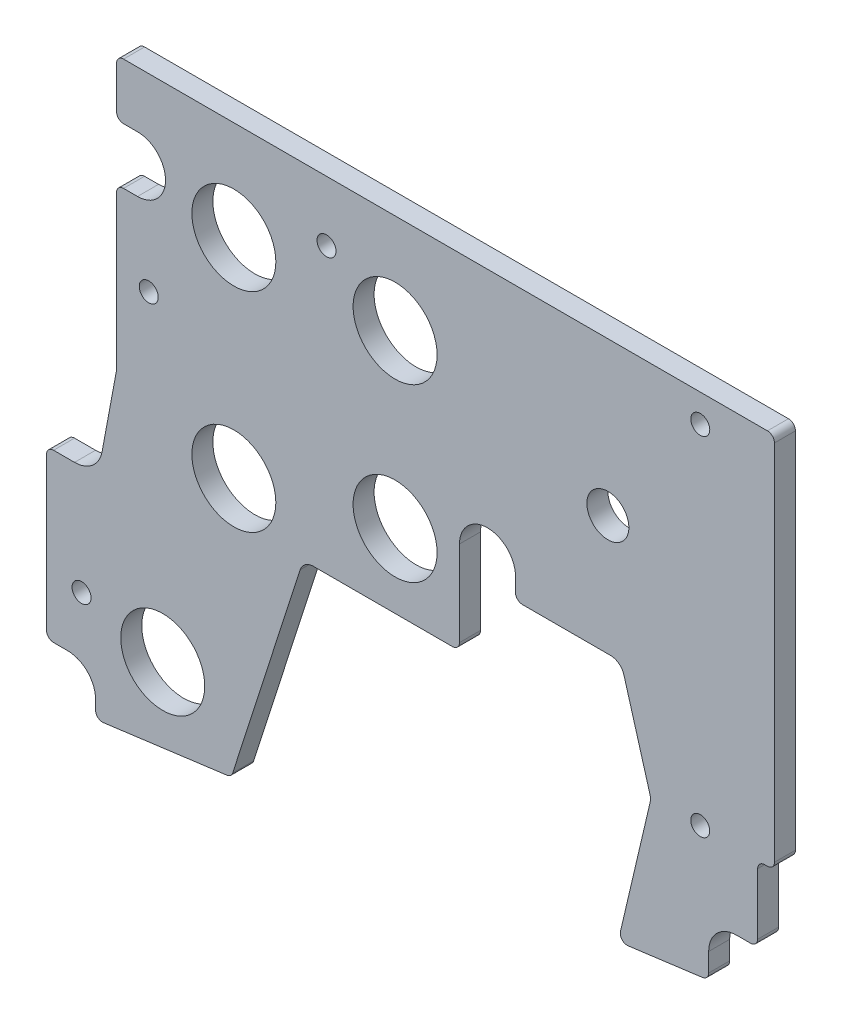
SolidWorks part; units mm, degrees
ref_plane "Front Plane" through (0, 0, 0) normal (0, 0, 1) x (1, 0, 0)
ref_plane "Top Plane" through (0, 0, 0) normal (0, 1, 0) x (1, 0, 0)
ref_plane "Right Plane" through (0, 0, 0) normal (1, 0, 0) x (0, 0, -1)
sketch "Sketch1" plane through (0, 0, 0) normal (0, 0, 1) x (1, 0, 0)
  line L24 (-1.5875, -85.5345) -> (-1.5875, -3.175)
  line L25 (-3.175, -1.5875) -> (-149.225, -1.5875)
  line L26 (-150.8125, -3.175) -> (-150.8125, -12.7)
  line L27 (-149.225, -14.2875) -> (-146.05, -14.2875)
  line L28 (-146.05, -26.9875) -> (-149.225, -26.9875)
  line L29 (-150.8125, -28.575) -> (-150.8125, -63.3539)
  line L30 (-150.8392, -63.6437) -> (-154.0942, -81.1696)
  line L31 (-160.3375, -86.36) -> (-165.1, -86.36)
  line L32 (-166.6875, -87.9475) -> (-166.6875, -122.5455)
  line L33 (-165.1, -124.133) -> (-161.925, -124.133)
  line L34 (-155.575, -130.483) -> (-155.575, -132.6404)
  line L35 (-153.7803, -134.2144) -> (-125.7711, -130.5269)
  line L36 (-124.467, -129.4389) -> (-109.1805, -81.8956)
  line L37 (-106.1579, -79.6925) -> (-74.6125, -79.6925)
  line L38 (-73.025, -78.105) -> (-73.025, -58.7375)
  line L39 (-60.325, -58.7375) -> (-60.325, -61.9125)
  line L40 (-58.7375, -63.5) -> (-38.7866, -63.5)
  line L41 (-35.7358, -65.7958) -> (-29.8313, -86.2841)
  line L42 (-29.7909, -87.8878) -> (-36.5223, -116.6102)
  line L43 (-34.7695, -118.5463) -> (-17.8903, -116.3241)
  line L44 (-16.51, -114.7502) -> (-16.51, -110.5169)
  line L45 (-10.16, -104.1528) -> (-6.985, -104.1528)
  line L46 (-5.3975, -102.5653) -> (-5.3975, -88.7095)
  line L47 (-3.81, -87.122) -> (-3.175, -87.122)
  line L48 (-1.5875, -85.5345) -> (-1.5875, -3.175)
  line L49 (-3.175, -1.5875) -> (-149.225, -1.5875)
  line L50 (-150.8125, -3.175) -> (-150.8125, -12.7)
  line L51 (-149.225, -14.2875) -> (-146.05, -14.2875)
  line L52 (-146.05, -26.9875) -> (-149.225, -26.9875)
  line L53 (-150.8125, -28.575) -> (-150.8125, -63.3539)
  line L54 (-150.8392, -63.6437) -> (-154.0942, -81.1696)
  line L55 (-160.3375, -86.36) -> (-165.1, -86.36)
  line L56 (-166.6875, -87.9475) -> (-166.6875, -122.5455)
  line L57 (-165.1, -124.133) -> (-161.925, -124.133)
  line L58 (-155.575, -130.483) -> (-155.575, -132.6404)
  line L59 (-153.7803, -134.2144) -> (-125.7711, -130.5269)
  line L60 (-124.467, -129.4389) -> (-109.1805, -81.8956)
  line L61 (-106.1579, -79.6925) -> (-74.6125, -79.6925)
  line L62 (-73.025, -78.105) -> (-73.025, -58.7375)
  line L63 (-60.325, -58.7375) -> (-60.325, -61.9125)
  line L64 (-58.7375, -63.5) -> (-38.7866, -63.5)
  line L65 (-35.7358, -65.7958) -> (-29.8313, -86.2841)
  line L66 (-29.7909, -87.8878) -> (-36.5223, -116.6102)
  line L67 (-34.7695, -118.5463) -> (-17.8903, -116.3241)
  line L68 (-16.51, -114.7502) -> (-16.51, -110.5169)
  line L69 (-10.16, -104.1528) -> (-6.985, -104.1528)
  line L70 (-5.3975, -102.5653) -> (-5.3975, -88.7095)
  line L71 (-3.81, -87.122) -> (-3.175, -87.122)
  arc A24 (-3.175, -87.122) -> (-1.5875, -85.5345) centre (-3.175, -85.5345) ccw
  arc A25 (-1.5875, -3.175) -> (-3.175, -1.5875) centre (-3.175, -3.175) ccw
  arc A26 (-149.225, -1.5875) -> (-150.8125, -3.175) centre (-149.225, -3.175) ccw
  arc A27 (-150.8125, -12.7) -> (-149.225, -14.2875) centre (-149.225, -12.7) ccw
  arc A28 (-146.05, -26.9875) -> (-146.05, -14.2875) centre (-146.05, -20.6375) ccw
  arc A29 (-149.225, -26.9875) -> (-150.8125, -28.575) centre (-149.225, -28.575) ccw
  arc A30 (-150.8392, -63.6437) -> (-150.8125, -63.3539) centre (-152.4, -63.3539) ccw
  arc A31 (-160.3375, -86.36) -> (-154.0942, -81.1696) centre (-160.3375, -80.01) ccw
  arc A32 (-165.1, -86.36) -> (-166.6875, -87.9475) centre (-165.1, -87.9475) ccw
  arc A33 (-166.6875, -122.5455) -> (-165.1, -124.133) centre (-165.1, -122.5455) ccw
  arc A34 (-155.575, -130.483) -> (-161.925, -124.133) centre (-161.925, -130.483) ccw
  arc A35 (-155.575, -132.6404) -> (-153.7803, -134.2144) centre (-153.9875, -132.6404) ccw
  arc A36 (-125.7711, -130.5269) -> (-124.467, -129.4389) centre (-125.9783, -128.953) ccw
  arc A37 (-106.1579, -79.6925) -> (-109.1805, -81.8956) centre (-106.1579, -82.8675) ccw
  arc A38 (-74.6125, -79.6925) -> (-73.025, -78.105) centre (-74.6125, -78.105) ccw
  arc A39 (-60.325, -58.7375) -> (-73.025, -58.7375) centre (-66.675, -58.7375) ccw
  arc A40 (-60.325, -61.9125) -> (-58.7375, -63.5) centre (-58.7375, -61.9125) ccw
  arc A41 (-35.7358, -65.7958) -> (-38.7866, -63.5) centre (-38.7866, -66.675) ccw
  arc A42 (-29.7909, -87.8878) -> (-29.8313, -86.2841) centre (-32.8822, -87.1633) ccw
  arc A43 (-36.5223, -116.6102) -> (-34.7695, -118.5463) centre (-34.9767, -116.9724) ccw
  arc A44 (-17.8903, -116.3241) -> (-16.51, -114.7502) centre (-18.0975, -114.7502) ccw
  arc A45 (-10.16, -104.1528) -> (-16.51, -110.5169) centre (-10.16, -110.5028) ccw
  arc A46 (-6.985, -104.1528) -> (-5.3975, -102.5653) centre (-6.985, -102.5653) ccw
  arc A47 (-3.81, -87.122) -> (-5.3975, -88.7095) centre (-3.81, -88.7095) ccw
  arc A48 (-3.175, -87.122) -> (-1.5875, -85.5345) centre (-3.175, -85.5345) ccw
  arc A49 (-1.5875, -3.175) -> (-3.175, -1.5875) centre (-3.175, -3.175) ccw
  arc A50 (-149.225, -1.5875) -> (-150.8125, -3.175) centre (-149.225, -3.175) ccw
  arc A51 (-150.8125, -12.7) -> (-149.225, -14.2875) centre (-149.225, -12.7) ccw
  arc A52 (-146.05, -26.9875) -> (-146.05, -14.2875) centre (-146.05, -20.6375) ccw
  arc A53 (-149.225, -26.9875) -> (-150.8125, -28.575) centre (-149.225, -28.575) ccw
  arc A54 (-150.8392, -63.6437) -> (-150.8125, -63.3539) centre (-152.4, -63.3539) ccw
  arc A55 (-160.3375, -86.36) -> (-154.0942, -81.1696) centre (-160.3375, -80.01) ccw
  arc A56 (-165.1, -86.36) -> (-166.6875, -87.9475) centre (-165.1, -87.9475) ccw
  arc A57 (-166.6875, -122.5455) -> (-165.1, -124.133) centre (-165.1, -122.5455) ccw
  arc A58 (-155.575, -130.483) -> (-161.925, -124.133) centre (-161.925, -130.483) ccw
  arc A59 (-155.575, -132.6404) -> (-153.7803, -134.2144) centre (-153.9875, -132.6404) ccw
  arc A60 (-125.7711, -130.5269) -> (-124.467, -129.4389) centre (-125.9783, -128.953) ccw
  arc A61 (-106.1579, -79.6925) -> (-109.1805, -81.8956) centre (-106.1579, -82.8675) ccw
  arc A62 (-74.6125, -79.6925) -> (-73.025, -78.105) centre (-74.6125, -78.105) ccw
  arc A63 (-60.325, -58.7375) -> (-73.025, -58.7375) centre (-66.675, -58.7375) ccw
  arc A64 (-60.325, -61.9125) -> (-58.7375, -63.5) centre (-58.7375, -61.9125) ccw
  arc A65 (-35.7358, -65.7958) -> (-38.7866, -63.5) centre (-38.7866, -66.675) ccw
  arc A66 (-29.7909, -87.8878) -> (-29.8313, -86.2841) centre (-32.8822, -87.1633) ccw
  arc A67 (-36.5223, -116.6102) -> (-34.7695, -118.5463) centre (-34.9767, -116.9724) ccw
  arc A68 (-17.8903, -116.3241) -> (-16.51, -114.7502) centre (-18.0975, -114.7502) ccw
  arc A69 (-10.16, -104.1528) -> (-16.51, -110.5169) centre (-10.16, -110.5028) ccw
  arc A70 (-6.985, -104.1528) -> (-5.3975, -102.5653) centre (-6.985, -102.5653) ccw
  arc A71 (-3.81, -87.122) -> (-5.3975, -88.7095) centre (-3.81, -88.7095) ccw
  dimension "D1" = 0
extrude "Boss-Extrude1" add sketch "Sketch1" along normal blind 4.7625
hole_wizard "#6 Clearance Hole1" positions "Sketch3" profile "Sketch2" hole size "#6" standard "ANSI Inch" end condition through all
sketch "Sketch3" plane through (0, 0, 4.7625) normal (0, 0, 1) x (1, 0, 0)
  point P0 (-103.1875, -15.24)
  point P3 (-18.415, -7.9375)
  point P6 (-143.51, -44.45)
  point P9 (-158.75, -111.125)
  point P12 (-18.415, -86.741)
sketch "Sketch2" plane through (-103.1875, -15.24, 4.7625) normal (1, 0, 0) x (0, -1, 0)
  line L0 (0, 0) -> (0, 4.7625)
  line L1 (0, 4.7625) -> (2.1526, 4.7625)
  line L2 (2.1526, 4.7625) -> (2.1526, 0)
  line L5 (2.1526, 0) -> (0, 0)
  line L11 (0, -6.35) -> (0, 107.95) construction
  dimension "Thru Hole Dia." = 4.3053
  dimension "Thru Hole Depth" = 4.7625
sketch "Sketch5" plane through (0, 0, 4.7625) normal (0, 0, 1) x (1, 0, 0)
  circle A0 centre (-124.206, -24.13) radius 9.525
  circle A1 centre (-87.63, -24.13) radius 9.525
  circle A2 centre (-87.63, -62.992) radius 9.525
  circle A3 centre (-124.206, -71.4375) radius 9.525
  circle A4 centre (-140.335, -115.57) radius 9.525
  circle A5 centre (-39.37, -36.322) radius 4.7625
  dimension "D1" = 19.05
  dimension "D2" = 9.525
extrude "Cut-Extrude1" cut sketch "Sketch5" against normal through all
